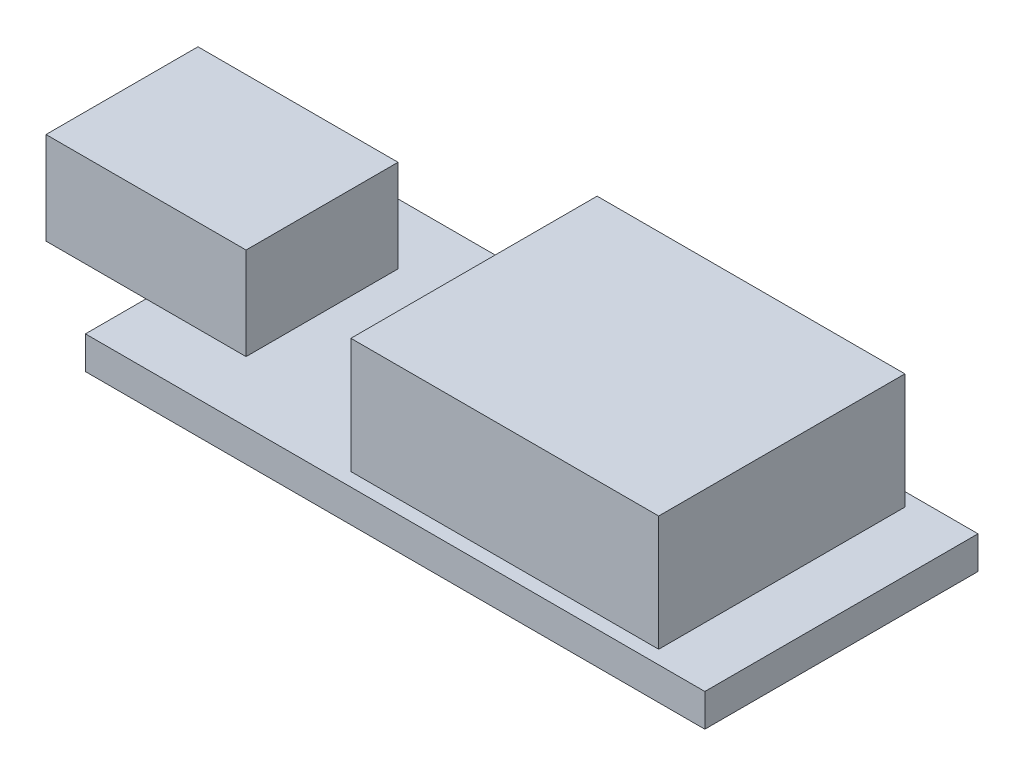
SolidWorks part; units mm, degrees
ref_plane "Front Plane" through (0, 0, 0) normal (0, 0, 1) x (1, 0, 0)
ref_plane "Top Plane" through (0, 0, 0) normal (0, 1, 0) x (1, 0, 0)
ref_plane "Right Plane" through (0, 0, 0) normal (1, 0, 0) x (0, 0, -1)
sketch "Sketch1" plane through (0, 0, 0) normal (0, 1, 0) x (1, 0, 0)
  line L1 (-16.1, 7.1) -> (16.1, 7.1)
  line L2 (-16.1, 7.1) -> (-16.1, -7.1)
  line L3 (-16.1, -7.1) -> (16.1, -7.1)
  line L4 (16.1, 7.1) -> (16.1, -7.1)
  line L5 (-16.1, 7.1) -> (16.1, -7.1) construction
  line L6 (-16.1, -7.1) -> (16.1, 7.1) construction
  circle A0 centre (-5.95, 0) radius 1.35
  point P0 (0, 0)
  dimension "D3" = 2.7
  dimension "D1" = 14.2
  dimension "D2" = 32.2
  dimension "D5" = 8.8
extrude "Boss-Extrude1" add sketch "Sketch1" along normal blind 1.7
sketch "Sketch2" plane through (0, 1.7, 0) normal (0, 1, 0) x (1, 0, 0)
  line L0 (16.1, -7.1) -> (16.1, 7.1) construction
  line L1 (-3, 6.4) -> (13, 6.4)
  line L2 (-3, 6.4) -> (-3, -6.4)
  line L3 (-3, -6.4) -> (13, -6.4)
  line L4 (13, 6.4) -> (13, -6.4)
  line L5 (-3, 6.4) -> (13, -6.4) construction
  line L6 (-3, -6.4) -> (13, 6.4) construction
  point P0 (5, 0)
  dimension "D1" = 12.8
  dimension "D2" = 16
  dimension "D3" = 3.1
extrude "Boss-Extrude2" add sketch "Sketch2" along normal blind 6
sketch "Sketch3" plane through (0, 1.7, 0) normal (0, 1, 0) x (1, 0, 0)
  line L0 (-16.1, 7.1) -> (-16.1, -7.1) construction
  line L1 (-21.3, 3.95) -> (-10.9, 3.95)
  line L2 (-21.3, 3.95) -> (-21.3, -3.95)
  line L3 (-21.3, -3.95) -> (-10.9, -3.95)
  line L4 (-10.9, 3.95) -> (-10.9, -3.95)
  line L5 (-21.3, 3.95) -> (-10.9, -3.95) construction
  line L6 (-21.3, -3.95) -> (-10.9, 3.95) construction
  point P0 (-16.1, 0)
  dimension "D1" = 5.2
  dimension "D2" = 7.9
extrude "Boss-Extrude3" add sketch "Sketch3" along normal blind 4.8
